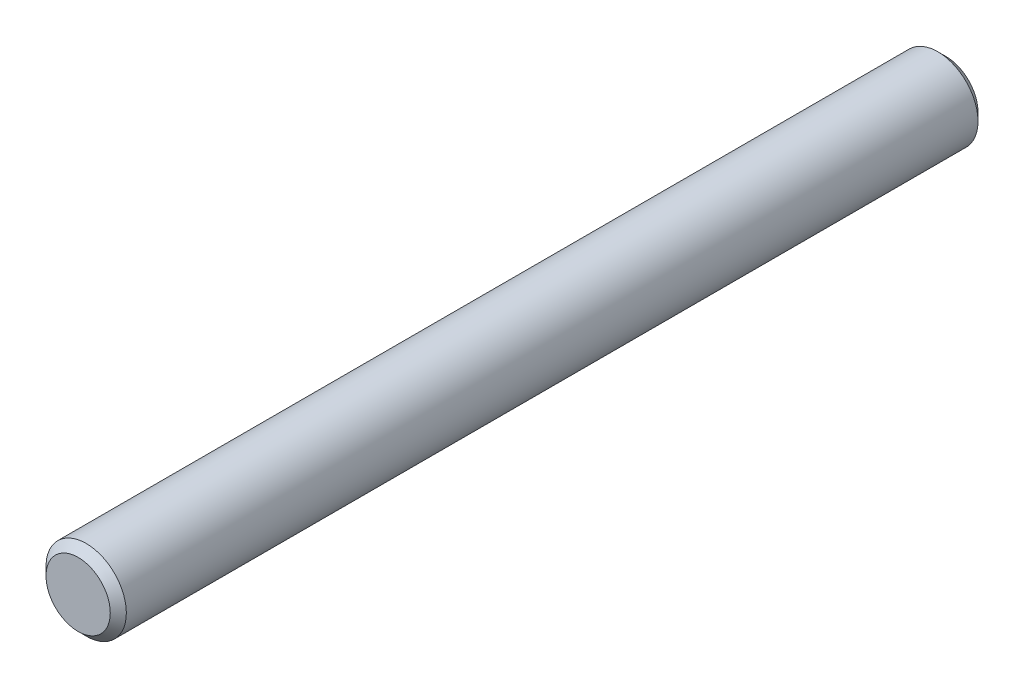
SolidWorks part; units mm, degrees
material "Plain Carbon Steel"
ref_plane "Front" through (0, 0, 0) normal (0, 0, 1) x (1, 0, 0)
ref_plane "Top" through (0, 0, 0) normal (0, 1, 0) x (1, 0, 0)
ref_plane "Right" through (0, 0, 0) normal (1, 0, 0) x (0, 0, -1)
sketch "Sketch1" plane through (0, 0, 0) normal (0, 0, 1) x (1, 0, 0)
  circle A0 centre (0, 0) radius 4.7625
  dimension "dia" = 9.525
extrude "Extrude1" add sketch "Sketch1" along normal mid plane 102.87
sketch "Sketch2" plane through (0, 0, 0) normal (1, 0, 0) x (0, 0, -1)
  line L0 (51.435, 4.7625) -> (48.895, 4.7625) construction
  line L1 (51.435, 4.7625) -> (-51.435, 4.7625) construction
  line L2 (48.895, 4.7625) -> (42.545, 4.7625) construction
  line L3 (42.545, 4.7625) -> (33.655, 4.7625) construction
  line L4 (33.655, 4.7625) -> (27.305, 4.7625) construction
  line L8 (38.1, 4.7625) -> (38.1, -4.7625) construction
  line L9 (-51.435, -4.7625) -> (51.435, -4.7625) construction
  line L10 (27.305, 4.7625) -> (18.415, 4.7625) construction
  line L11 (18.415, 4.7625) -> (12.065, 4.7625) construction
  line L12 (12.065, 4.7625) -> (3.175, 4.7625) construction
  line L13 (3.175, 4.7625) -> (-3.175, 4.7625) construction
  line L14 (-3.175, 4.7625) -> (-12.065, 4.7625) construction
  line L15 (26.035, 4.7625) -> (26.035, -4.7625) construction
  line L16 (10.795, 4.7625) -> (10.795, -4.7625) construction
  line L17 (-4.445, 4.7625) -> (-4.445, -4.7625) construction
  line L18 (-12.065, 4.7625) -> (-18.415, 4.7625) construction
  line L19 (35.6362, 4.7625) -> (40.5638, 4.7625) construction
  line L20 (35.6362, 4.7625) -> (35.6362, -4.7625) construction
  line L21 (35.6362, -4.7625) -> (40.5638, -4.7625) construction
  line L22 (40.5638, 4.7625) -> (40.5638, -4.7625) construction
  line L23 (-18.415, 4.7625) -> (-27.305, 4.7625) construction
  line L24 (-27.305, 4.7625) -> (-33.655, 4.7625) construction
  line L25 (-33.655, 4.7625) -> (-42.545, 4.7625) construction
  line L26 (-42.545, 4.7625) -> (-48.895, 4.7625) construction
  line L27 (-19.685, 4.7625) -> (-19.685, -4.7625) construction
  line L28 (-34.925, 4.7625) -> (-34.925, -4.7625) construction
  point P0 (-51.435, 4.7625)
  point P1 (51.435, 4.7625)
  point P30 (38.1, 4.7625)
  dimension "D1" = 2.54
  dimension "D2" = 6.35
  dimension "D3" = 8.89
  dimension "D4" = 6.35
  dimension "D5" = 8.89
  dimension "D6" = 6.35
  dimension "D7" = 8.89
  dimension "D8" = 6.35
  dimension "D9" = 8.89
  dimension "D10" = 4.9276
  dimension "D11" = 1.27
  dimension "D12" = 1.27
  dimension "D13" = 1.27
  dimension "D14" = 6.35
  dimension "D15" = 6.35
  dimension "D16" = 8.89
  dimension "D17" = 8.89
  dimension "D18" = 6.35
  dimension "D19" = 1.27
  dimension "D20" = 1.27
chamfer "Chamfer1" distance 0.9525 angle 45 2 edges at (4.7625, 0, -51.435) (4.7625, 0, 51.435)
equation "\"D1@Chamfer1\" = \"dia@Sketch1\" * .1"
